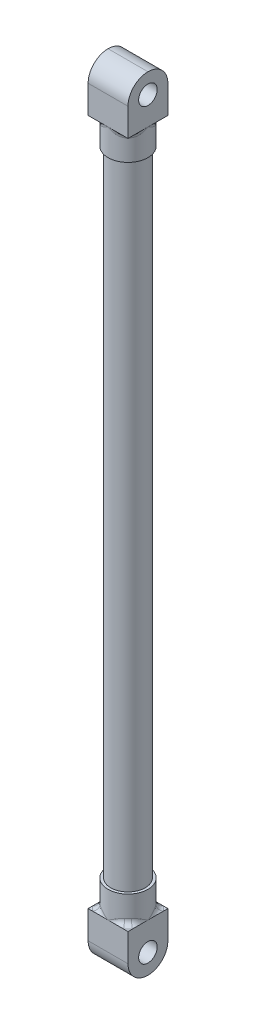
SolidWorks part; units mm, degrees
ref_plane "Front Plane" through (0, 0, 0) normal (0, 0, 1) x (1, 0, 0)
ref_plane "Top Plane" through (0, 0, 0) normal (0, 1, 0) x (1, 0, 0)
ref_plane "Right Plane" through (0, 0, 0) normal (1, 0, 0) x (0, 0, -1)
sketch "Sketch1" plane through (0, 0, 0) normal (0, 1, 0) x (1, 0, 0)
  circle A0 centre (0, 0) radius 6.5
extrude "Boss-Extrude1" add sketch "Sketch1" along normal blind 119.2
sketch "Sketch2" plane through (0, 119.2, 0) normal (0, -1, 0) x (-1, 0, 0)
  circle A0 centre (0, 0) radius 7.5
extrude "Boss-Extrude2" add sketch "Sketch2" against normal blind 10
sketch "Sketch3" plane through (0, 129.2, 0) normal (0, -1, 0) x (-1, 0, 0)
  line L1 (-7.5, 7.5) -> (7.5, 7.5)
  line L2 (-7.5, 7.5) -> (-7.5, -7.5)
  line L3 (-7.5, -7.5) -> (7.5, -7.5)
  line L4 (7.5, 7.5) -> (7.5, -7.5)
  line L5 (-7.5, 7.5) -> (7.5, -7.5) construction
  line L6 (-7.5, -7.5) -> (7.5, 7.5) construction
  point P0 (0, 0)
extrude "Boss-Extrude3" add sketch "Sketch3" against normal blind 18
fillet "Fillet2" radius 7.5 1 edges at (0, 147.2, -7.5) type face fillet first side face at (0, 147.2, 0) second side face at (0, 136.4, -7.5)
fillet "Fillet3" radius 7.5 1 edges at (0, 147.2, 7.5) type face fillet first side face at (0, 147.2, 3.75) second side face at (0, 136.4, 7.5)
sketch "Sketch4" plane through (7.5, 0, 0) normal (1, 0, 0) x (0, 0, -1)
  circle A0 centre (0, 139.7) radius 3.5
extrude "Cut-Extrude1" cut sketch "Sketch4" against normal up to surface (15 mm away) up to face at (-7.5, 136.2178, 0)
fillet "Fillet5" radius 2 4 edges at (5.3033, 129.2, -5.3033) (5.3033, 129.2, 5.3033) (-5.3033, 129.2, 5.3033) (-5.3033, 129.2, -5.3033)
mirror "Mirror2" about plane through (0, 0, 0) normal (0, 1, 0) of "Fillet2", "Cut-Extrude1", "Fillet3", "Fillet5", "Boss-Extrude3", "Boss-Extrude2", "Boss-Extrude1"
ref_point "Point1"
ref_point "Point2"
ref_axis "Axis1" through (7.5, -139.7, 0) along (-1, 0, 0)
